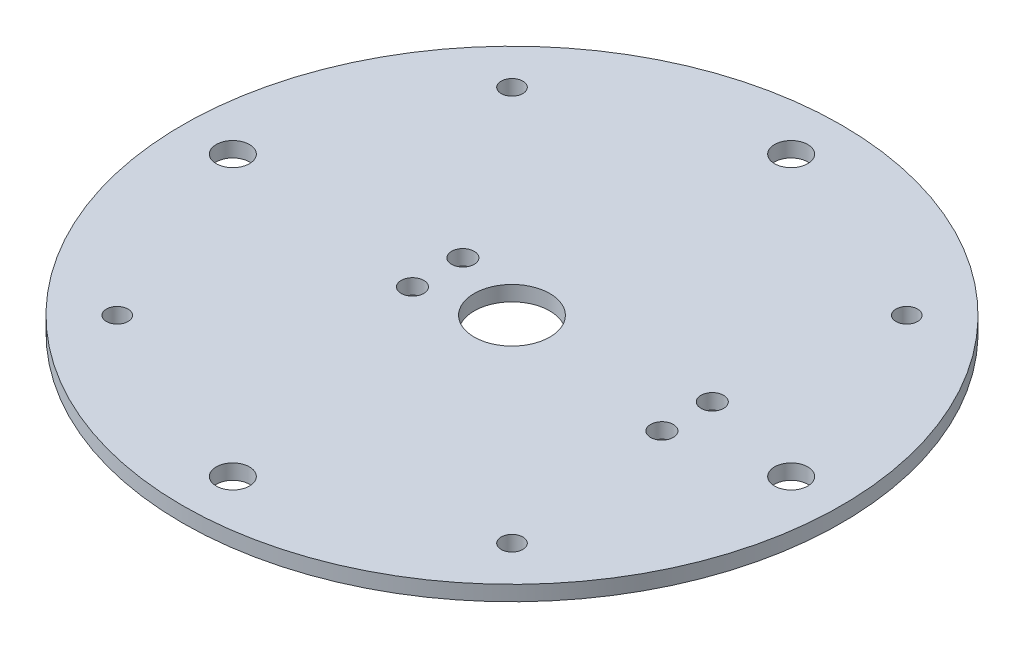
SolidWorks part; units mm, degrees
ref_plane "Front Plane" through (0, 0, 0) normal (0, 0, 1) x (1, 0, 0)
ref_plane "Top Plane" through (0, 0, 0) normal (0, 1, 0) x (1, 0, 0)
ref_plane "Right Plane" through (0, 0, 0) normal (1, 0, 0) x (0, 0, -1)
sketch "Sketch1" plane through (0, 0, 0) normal (0, 1, 0) x (1, 0, 0)
  circle A0 centre (0, 0) radius 65.4
  dimension "Diameter" = 130.8
extrude "Boss-Extrude1" add sketch "Sketch1" along normal mid plane 3
hole_wizard "M6 Clearance Hole1" positions "Sketch8" profile "Sketch9" hole size "M6" standard "ANSI Metric" end condition up to next
sketch "Sketch8" plane through (0, 1.5, 0) normal (0, 1, 0) x (1, 0, 0)
  line L0 (0, 0) -> (55.4, 0) construction
  point P0 (55.4, 0)
  dimension "ThreadedHoleDistance" = 55.4
sketch "Sketch9" plane through (55.4, 1.5, 0) normal (1, 0, 0) x (0, 0, 1)
  line L0 (0, 0) -> (0, 3)
  line L1 (0, 3) -> (3.3, 3)
  line L2 (3.3, 3) -> (3.3, 0)
  line L5 (3.3, 0) -> (0, 0)
  line L11 (0, -6.35) -> (0, 107.95) construction
  dimension "Thru Hole Dia." = 6.6
  dimension "Thru Hole Depth" = 3
pattern_circular "CirPattern2" count 4 over 360 about axis through (0, 1.5, 0) along (0, -1, 0) of "M6 Clearance Hole1" reverse direction yes
sketch "Sketch5" plane through (0, 1.5, 0) normal (0, 1, 0) x (1, 0, 0)
  line L0 (0, 0) -> (65.4, 0) construction
  line L2 (0, 0) -> (39.1737, 39.1737) construction
  circle A0 centre (0, 0) radius 65.4 construction
  dimension "D1" = 45
  dimension " NoseShellHoleRadius" = 55.4
hole_wizard "M4 Clearance Hole1" positions "Sketch6" profile "Sketch7" hole size "M4" standard "ANSI Metric" end condition up to next
sketch "Sketch6" plane through (0, 1.5, 0) normal (0, 1, 0) x (1, 0, 0)
  point P0 (39.1737, 39.1737)
sketch "Sketch7" plane through (39.1737, 1.5, -39.1737) normal (1, 0, 0) x (0, 0, 1)
  line L0 (0, 0) -> (0, 3)
  line L1 (0, 3) -> (2.15, 3)
  line L2 (2.15, 3) -> (2.15, 0)
  line L5 (2.15, 0) -> (0, 0)
  line L11 (0, -6.35) -> (0, 107.95) construction
  dimension "Thru Hole Dia." = 4.3
  dimension "Thru Hole Depth" = 3
pattern_circular "CirPattern1" count 4 over 360 about axis through (0, 1.5, 0) along (0, -1, 0) of "M4 Clearance Hole1" reverse direction yes
sketch "Sketch10" plane through (0, 1.5, 0) normal (0, 1, 0) x (1, 0, 0)
  circle A0 centre (0, 0) radius 7.5
  dimension "D1" = 15
extrude "Cut-Extrude1" cut sketch "Sketch10" against normal through all
sketch "Sketch11" plane through (0, -1.5, 0) normal (0, -1, 0) x (1, 0, 0)
  circle A0 centre (-14.75, -5) radius 2.25
  arc A1 (-16.7656, -6) -> (-16.7656, -4) centre (-14.75, -5) ccw construction
  circle A2 centre (-14.75, 5) radius 2.25
  circle A3 centre (34.75, -5) radius 2.25
  circle A4 centre (34.75, 5) radius 2.25
  arc A5 (-16.7656, 4) -> (-16.7656, 6) centre (-14.75, 5) ccw construction
  arc A6 (36.7656, 6) -> (36.7656, 4) centre (34.75, 5) ccw construction
  arc A7 (36.7656, -4) -> (36.7656, -6) centre (34.75, -5) ccw construction
extrude "Cut-Extrude2" cut sketch "Sketch11" against normal through all
sketch "Sketch12" plane through (0, 1.5, 0) normal (0, 1, 0) x (1, 0, 0)
  circle A0 centre (0, 0) radius 65.4 construction
  circle A1 centre (0, 0) radius 65.4
